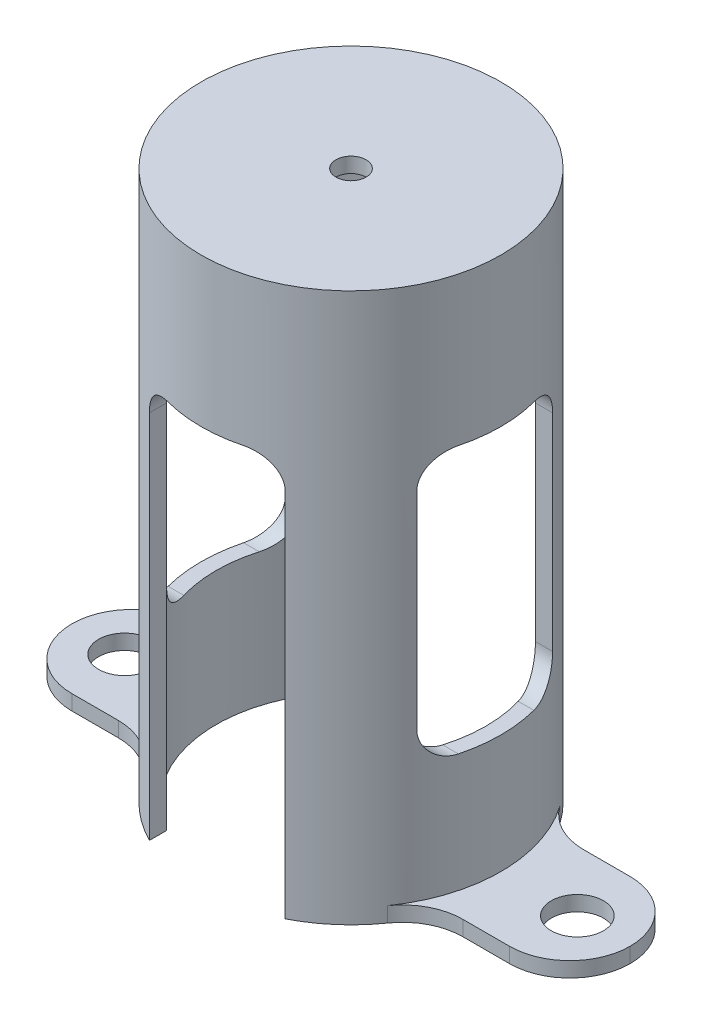
SolidWorks part; units mm, degrees
material "6061-T6 (SS)"
ref_plane "Front Plane" through (0, 0, 0) normal (0, 0, 1) x (1, 0, 0)
ref_plane "Top Plane" through (0, 0, 0) normal (0, 1, 0) x (1, 0, 0)
ref_plane "Right Plane" through (0, 0, 0) normal (1, 0, 0) x (0, 0, -1)
sketch "Sketch2" plane through (0, 0, 0) normal (0, 1, 0) x (1, 0, 0)
  circle A1 centre (0, 0) radius 9.9375
  dimension "D2" = 19.875
extrude "Boss-Extrude1" add sketch "Sketch2" along normal blind 35.384
sketch "Sketch4" plane through (0, 35.384, 0) normal (0, 1, 0) x (1, 0, 0)
  circle A0 centre (0, 0) radius 1
  dimension "D1" = 2
extrude "Cut-Extrude2" cut sketch "Sketch4" against normal through all
sketch "Sketch11" plane through (0, 0, 0) normal (0, -1, 0) x (1, 0, 0)
  line L0 (9.0969, 4) -> (18.5, 4)
  line L1 (-18.5, 4) -> (-9.0969, 4)
  line L2 (-18.5, 4) -> (-18.5, -4)
  line L3 (-18.5, -4) -> (-9.0969, -4)
  line L4 (18.5, 4) -> (18.5, -4)
  line L5 (-18.5, 4) -> (18.5, -4) construction
  line L6 (-18.5, -4) -> (18.5, 4) construction
  line L7 (9.0969, -4) -> (18.5, -4)
  arc A0 (9.0969, 4) -> (-9.0969, 4) centre (0, 0) ccw
  circle A1 centre (0, 0) radius 8.9375
  arc A2 (-9.0969, -4) -> (9.0969, -4) centre (0, 0) ccw
  point P0 (0, 0)
  dimension "D3" = 19.875
  dimension "D4" = 17.875
  dimension "D1" = 8
  dimension "D2" = 37
extrude "Boss-Extrude2" add sketch "Sketch11" along normal blind 1
sketch "Sketch12" plane through (0, 0, 0) normal (0, -1, 0) x (1, 0, 0)
  circle A0 centre (0, 0) radius 8.9375
  dimension "D1" = 17.875
extrude "Cut-Extrude7" cut sketch "Sketch12" against normal blind 34.384
ref_plane "Plane4" through (0, 0, 30) normal (0, 0, 1) x (1, 0, 0)
sketch "Sketch13" plane through (0, 0, 30) normal (0, 0, 1) x (1, 0, 0)
  line L0 (0, -10.9313) -> (0, 10.9313) construction
  line L1 (-4.5, 25.538) -> (4.5, 25.538)
  line L2 (-4.5, 25.538) -> (-4.5, -1)
  line L3 (-4.5, -1) -> (4.5, -1)
  line L4 (4.5, 25.538) -> (4.5, -1)
  line L5 (-4.5, 25.538) -> (4.5, -1) construction
  line L6 (-4.5, -1) -> (4.5, 25.538) construction
  line L7 (-9.0969, -1) -> (9.0969, -1) construction
  point P0 (0, 12.269)
  dimension "D1" = 26.538
  dimension "D2" = 9
extrude "Cut-Extrude8" cut sketch "Sketch13" against normal through all
ref_plane "Plane5" through (30, 0, 0) normal (1, 0, 0) x (0, 0, -1)
sketch "Sketch14" plane through (30, 0, 0) normal (1, 0, 0) x (0, 0, -1)
  line L0 (0, 10.9313) -> (0, -10.9313) construction
  line L1 (-4.5, 25.538) -> (4.5, 25.538)
  line L2 (-4.5, 25.538) -> (-4.5, 7.846)
  line L3 (-4.5, 7.846) -> (4.5, 7.846)
  line L4 (4.5, 25.538) -> (4.5, 7.846)
  line L5 (-4.5, 25.538) -> (4.5, 7.846) construction
  line L6 (-4.5, 7.846) -> (4.5, 25.538) construction
  line L7 (4, -1) -> (-4, -1) construction
  point P0 (0, 16.692)
  dimension "D2" = 9
  dimension "D1" = 17.692
  dimension "D3" = 17.692
extrude "Cut-Extrude9" cut sketch "Sketch14" against normal through all
fillet "Fillet3" radius 2 12 edges at (4.5, 25.538, -8.2911) (-4.5, 25.538, -8.2911) (-4.5, 25.538, 8.2911) (4.5, 25.538, 8.2911) (-8.2911, 25.538, 4.5) (-8.2911, 25.538, -4.5) (-8.2911, 7.846, -4.5) (-8.2911, 7.846, 4.5) (8.2911, 7.846, 4.5) (8.2911, 25.538, 4.5) (8.2911, 25.538, -4.5) (8.2911, 7.846, -4.5)
fillet "Fillet4" radius 4 8 edges at (9.0969, -0.5, -4) (18.5, -0.5, -4) (9.0969, -0.5, 4) (18.5, -0.5, 4) (-9.0969, -0.5, 4) (-18.5, -0.5, -4) (-9.0969, -0.5, -4) (-18.5, -0.5, 4)
sketch "Sketch15" plane through (0, 0, 0) normal (0, 1, 0) x (1, 0, 0)
  line L0 (-10.9313, 0) -> (10.9313, 0) construction
  circle A0 centre (-15, 0) radius 1.7272
  circle A1 centre (15, 0) radius 1.7272
  dimension "D3" = 3.4544
  dimension "D4" = 3.4544
  dimension "D1" = 15
  dimension "D2" = 15
extrude "Cut-Extrude10" cut sketch "Sketch15" against normal up to next
equation "\"FrangiboltTotalDiameter\"= 0.625in"
equation "\"FrangiboltTotalLength\"= 0.960in"
equation "\"FrangiboltThruHoleDiameter\"= 0.169in"
equation "\"EnclosureWallThickness\"= 1mm"
equation "\"EnclosureWallSpacing\"= 1mm"
equation "\"EnclosureInnerDiameter\"= \"FrangiboltTotalDiameter\" + 2 * \"EnclosureWallSpacing\""
equation "\"EnclosureOuterDiameter\"= \"FrangiboltTotalDiameter\" + 2 * \"EnclosureWallSpacing\" + 2 * \"EnclosureWallThickness\""
equation "\"EnclosureTotalLength\"= \"FrangiboltTotalLength\" + \"DamperLength\" + \"EnclosureWallThickness\""
equation "\"D2@Sketch2\"=\"EnclosureOuterDiameter\""
equation "\"D1@Boss-Extrude1\"=\"EnclosureTotalLength\""
equation "\"DamperLength\"= 10mm"
equation "\"EnclosureLip\"= 5mm"
equation "\"FrangiboltBoxWidth\"= 7mm"
equation "\"EnclosureMountingStandoff\"= 37mm"
equation "\"D2@Sketch11\"=\"EnclosureMountingStandoff\""
equation "\"D3@Sketch11\"=\"EnclosureOuterDiameter\""
equation "\"D4@Sketch11\"=\"EnclosureInnerDiameter\""
equation "\"D1@Boss-Extrude2\"=\"EnclosureWallThickness\""
equation "\"D1@Sketch12\"=\"EnclosureInnerDiameter\""
equation "\"D1@Cut-Extrude7\"=\"EnclosureTotalLength\"-\"EnclosureWallThickness\""
equation "\"D1@Sketch13\"=\"EnclosureTotalLength\"*0.75"
equation "\"D2@Sketch13\"=\"FrangiboltBoxWidth\"+2mm"
equation "\"D1@Sketch14\"=\"EnclosureTotalLength\"*0.5"
equation "\"D2@Sketch14\"=\"FrangiboltBoxWidth\"+2mm"
equation "\"D3@Sketch14\"=\"EnclosureTotalLength\"*0.5"
equation "\"EnclosureMountingHoleDiameter\"= 0.1360in'#29 Tap Drill"
equation "\"D3@Sketch15\"=\"EnclosureMountingHoleDiameter\""
equation "\"D4@Sketch15\"=\"EnclosureMountingHoleDiameter\""
